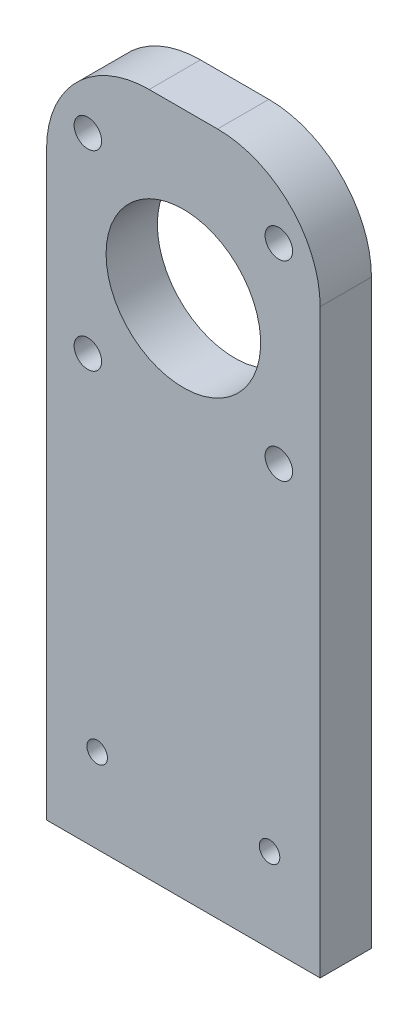
SolidWorks part; units mm, degrees
ref_plane "Front Plane" through (0, 0, 0) normal (0, 0, 1) x (1, 0, 0)
ref_plane "Top Plane" through (0, 0, 0) normal (0, 1, 0) x (1, 0, 0)
ref_plane "Right Plane" through (0, 0, 0) normal (1, 0, 0) x (0, 0, -1)
sketch "Sketch2" plane through (0, 0, 0) normal (0, 0, 1) x (1, 0, 0)
  line L0 (41.4, 15.6363) -> (9.4, 15.6363) construction
  line L1 (0, 0) -> (50.8, 0)
  line L2 (0, 0) -> (0, 127)
  line L3 (0, 127) -> (50.8, 127)
  line L4 (50.8, 0) -> (50.8, 127)
  circle A0 centre (25.4, 96.5708) radius 14.351
  circle A1 centre (43.1292, 114.3) radius 2.5527
  circle A2 centre (7.6708, 114.3) radius 2.5527
  circle A3 centre (7.6708, 78.8416) radius 2.5527
  circle A4 centre (43.1292, 78.8416) radius 2.5527
  circle A5 centre (41.4, 15.6363) radius 1.905
  circle A6 centre (9.4, 15.6363) radius 1.905
  point P19 (25.4, 15.6363)
  point P20 (25.4, 0)
  dimension "D4" = 28.702
  dimension "D5" = 5.1054
  dimension "D7" = 5.1054
  dimension "D8" = 5.1054
  dimension "D9" = 5.1054
  dimension "D3" = 35.4584
  dimension "D6" = 35.4584
  dimension "D12" = 12.7
  dimension "D16" = 3.81
  dimension "D17" = 3.81
  dimension "D18" = 32
  dimension "D1" = 127
  dimension "D2" = 50.8
  dimension "D10" = 35.4584
  dimension "D11" = 35.4584
  dimension "D13" = 17.7292
  dimension "D14" = 17.7292
  dimension "D15" = 17.7292
extrude "Boss-Extrude3" add sketch "Sketch2" along normal blind 9.525
fillet "Fillet1" radius 19.05 1 edges at (50.8, 127, 4.7625)
fillet "Fillet4" radius 19.05 1 edges at (0, 127, 4.7625)
